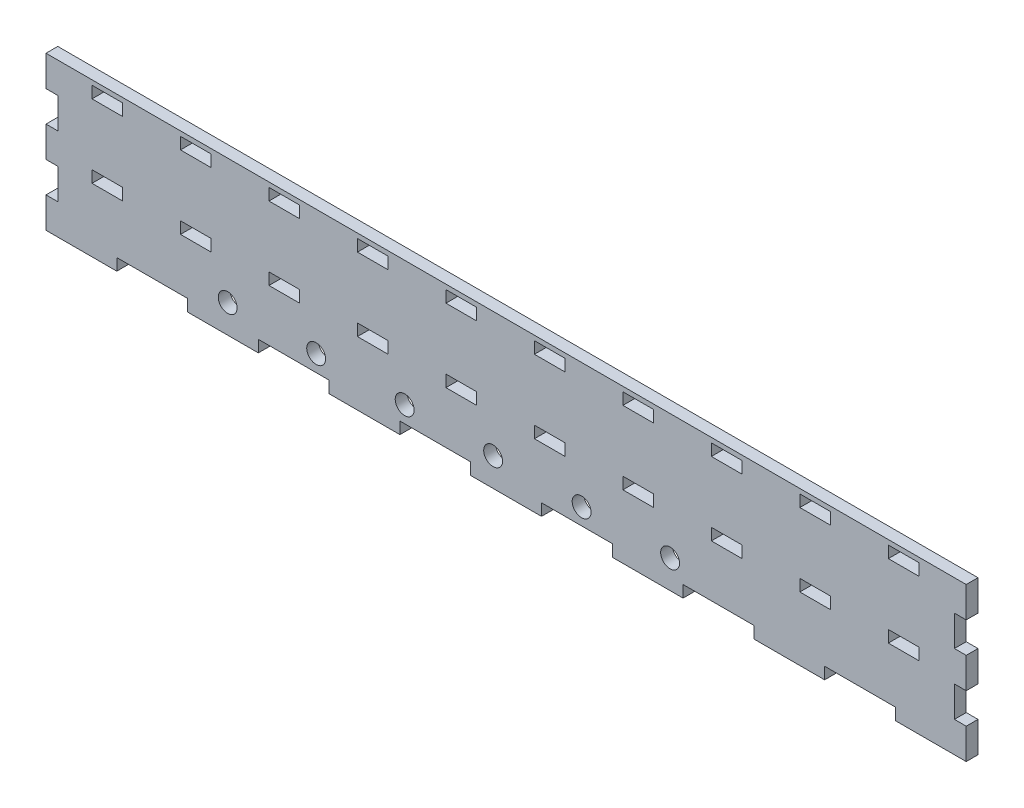
SolidWorks part; units mm, degrees
ref_plane "Plan de face" through (0, 0, 0) normal (0, 0, 1) x (1, 0, 0)
ref_plane "Plan de dessus" through (0, 0, 0) normal (0, 1, 0) x (1, 0, 0)
ref_plane "Plan de droite" through (0, 0, 0) normal (1, 0, 0) x (0, 0, -1)
sketch "Esquisse1" plane through (0, 0, 0) normal (0, 0, 1) x (1, 0, 0)
  line L1 (0, 0) -> (390, 0)
  line L2 (0, 0) -> (0, -65)
  line L3 (0, -65) -> (390, -65)
  line L4 (390, 0) -> (390, -65)
  dimension "D1" = 390
  dimension "D2" = 65
extrude "Boss.-Extru.1" add sketch "Esquisse1" along normal blind 5
sketch "Esquisse2" plane through (0, 0, 5) normal (0, 0, 1) x (1, 0, 0)
  line L0 (0, -65) -> (390, -65) construction
  line L1 (30, -65) -> (60, -65)
  line L2 (30, -65) -> (30, -60)
  line L3 (30, -60) -> (60, -60)
  line L4 (60, -65) -> (60, -60)
  line L5 (0, 0) -> (390, 0) construction
  line L6 (0, 0) -> (0, -65) construction
  dimension "D1" = 390
  dimension "D2" = 30
  dimension "D3" = 30
  dimension "D4" = 5
extrude "Enlèv. mat.-Extru.1" cut sketch "Esquisse2" against normal blind 5
pattern_linear "Répétition linéaire1" count 6 spacing 60 along (1, 0, 0) of "Enlèv. mat.-Extru.1"
sketch "Esquisse3" plane through (0, 0, 5) normal (0, 0, 1) x (1, 0, 0)
  line L0 (0, 0) -> (0, -65) construction
  line L1 (0, -52) -> (5, -52)
  line L2 (0, -52) -> (0, -39)
  line L3 (0, -39) -> (5, -39)
  line L4 (5, -52) -> (5, -39)
  line L5 (0, 0) -> (0, -65) construction
  line L6 (0, -65) -> (30, -65) construction
  dimension "D4" = 5
  dimension "D1" = 65
  dimension "D2" = 13
  dimension "D3" = 13
extrude "Enlèv. mat.-Extru.2" cut sketch "Esquisse3" against normal blind 5
pattern_linear "Répétition linéaire2" count 2 spacing 26 along (0, 1, 0) of "Enlèv. mat.-Extru.2"
ref_plane "Plan1" through (195, 0, 0) normal (-1, 0, 0) x (0, 0, 1)
mirror "Symétrie1" about plane through (195, 0, 0) normal (-1, 0, 0) of "Répétition linéaire2"
sketch "Esquisse4" plane through (0, 0, 5) normal (0, 0, 1) x (1, 0, 0)
  line L0 (0, -52) -> (0, -65) construction
  line L1 (60, -65) -> (90, -65) construction
  circle A0 centre (77, -53) radius 4
  dimension "D3" = 8
  dimension "D1" = 77
  dimension "D2" = 12
extrude "Enlèv. mat.-Extru.3" cut sketch "Esquisse4" against normal blind 5
pattern_linear "Répétition linéaire3" count 6 spacing 37.5 along (1, 0, 0) of "Enlèv. mat.-Extru.3"
sketch "Esquisse5" plane through (0, 0, 5) normal (0, 0, 1) x (1, 0, 0)
  line L0 (0, -52) -> (0, -65) construction
  line L1 (57, -33) -> (70, -33)
  line L2 (57, -33) -> (57, -38)
  line L3 (57, -38) -> (70, -38)
  line L4 (70, -33) -> (70, -38)
  line L5 (60, -65) -> (90, -65) construction
  line L7 (57, -2) -> (70, -2)
  line L8 (57, -2) -> (57, -7)
  line L9 (57, -7) -> (70, -7)
  line L10 (70, -2) -> (70, -7)
  dimension "D3" = 13
  dimension "D1" = 70
  dimension "D2" = 5
  dimension "D4" = 32
  dimension "D5" = 26
  dimension "D6" = 5
extrude "Enlèv. mat.-Extru.4" cut sketch "Esquisse5" against normal blind 5
pattern_linear "Répétition linéaire4" count 2 spacing 37.5 along (-1, 0, 0) count 9 spacing 37.5 along (1, 0, 0) of "Enlèv. mat.-Extru.4"
equation "\"D1@Esquisse1\"=400-10"
equation "\"D2@Esquisse2\"=\"D1@Esquisse2\"/13"
equation "\"D3@Esquisse2\"=\"D1@Esquisse2\"/13"
equation "\"D2@Esquisse3\"=\"D1@Esquisse3\"/5"
equation "\"D3@Esquisse3\"=\"D1@Esquisse3\"/5"
equation "\"D6@Esquisse5\"=\"D2@Esquisse5\""
